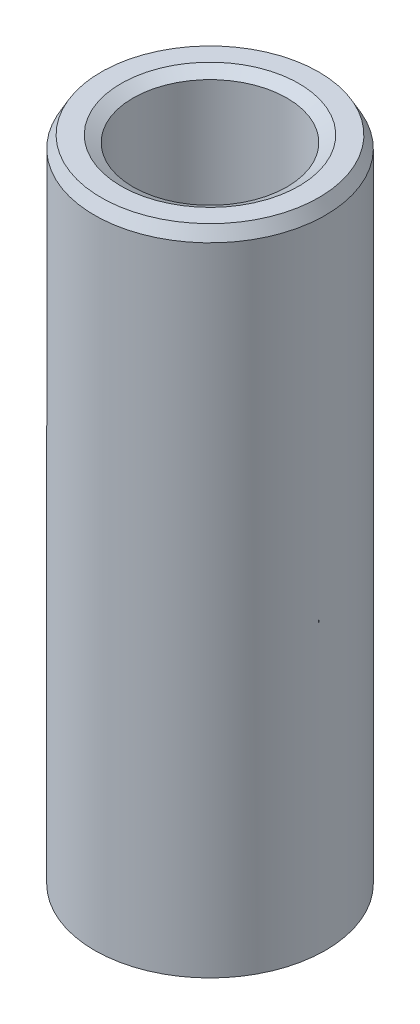
SolidWorks part; units mm, degrees
ref_plane "Front Plane" through (0, 0, 0) normal (0, 0, 1) x (1, 0, 0)
ref_plane "Top Plane" through (0, 0, 0) normal (0, 1, 0) x (1, 0, 0)
ref_plane "Right Plane" through (0, 0, 0) normal (1, 0, 0) x (0, 0, -1)
sketch "Sketch1" plane through (0, 0, 0) normal (0, 1, 0) x (1, 0, 0)
  circle A0 centre (0, 0) radius 37.5
  dimension "SLEEVE_OD" = 75
extrude "Boss-Extrude1" add sketch "Sketch1" along normal blind 212.7586
sketch "Sketch2" plane through (0, 0, 0) normal (0, 1, 0) x (1, 0, 0)
  circle A0 centre (0, 0) radius 25.0032
  dimension "BORE_D" = 50.0063
extrude "Cut-Extrude1" cut sketch "Sketch2" along normal through all
chamfer "Chamfer1" distance 3.8719 angle 29.131 4 edges at (0, 212.7586, 25.0032) (0, 0, 25.0032) (0, 0, 37.5) (0, 212.7586, 37.5) first distance on face at (0, 212.7586, 25.0032) first distance on face at (0, 0, 25.0032) first distance on face at (0, 212.7586, 37.5)
